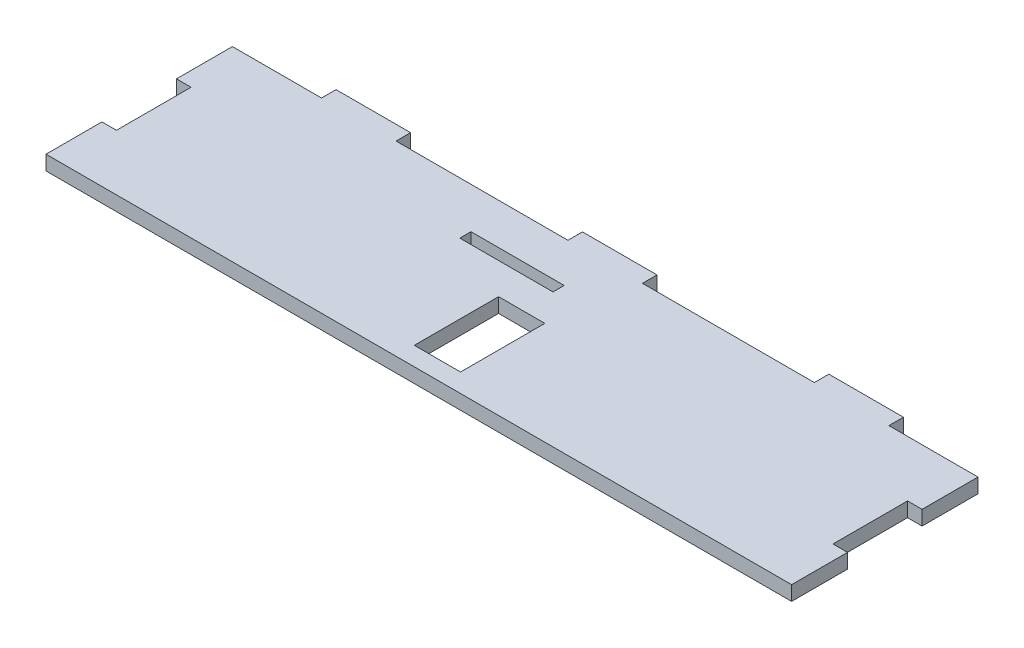
SolidWorks part; units mm, degrees
material "Very Low Density PE (SS)"
ref_plane "Front Plane" through (0, 0, 0) normal (0, 0, 1) x (1, 0, 0)
ref_plane "Top Plane" through (0, 0, 0) normal (0, 1, 0) x (1, 0, 0)
ref_plane "Right Plane" through (0, 0, 0) normal (1, 0, 0) x (0, 0, -1)
sketch "Sketch1" plane through (0, 0, 0) normal (0, 1, 0) x (1, 0, 0)
  line L0 (0, -25) -> (0, 26.95) construction
  line L1 (-100, 25) -> (-76.1, 25)
  line L2 (-100, 25) -> (-100, 10)
  line L3 (-100, -25) -> (100, -25)
  line L4 (100, 25) -> (100, 10)
  line L5 (-100, 25) -> (100, -25) construction
  line L6 (-100, -25) -> (100, 25) construction
  line L7 (76.1, 28.9) -> (56.1, 28.9)
  line L9 (-76.1, 25) -> (-76.1, 28.9)
  line L10 (-76.1, 28.9) -> (-56.1, 28.9)
  line L11 (-56.1, 25) -> (-56.1, 28.9)
  line L12 (56.1, 25) -> (56.1, 28.9)
  line L14 (76.1, 25) -> (76.1, 28.9)
  line L15 (-56.1, 25) -> (-10, 25)
  line L16 (76.1, 25) -> (100, 25)
  line L17 (10, 25) -> (56.1, 25)
  line L18 (-10, 28.9) -> (10, 28.9)
  line L19 (-10, 28.9) -> (-10, 25)
  line L21 (10, 28.9) -> (10, 25)
  line L22 (-10, 28.9) -> (10, 25) construction
  line L23 (-10, 25) -> (10, 28.9) construction
  line L24 (-100, 0) -> (100, 0) construction
  line L29 (-100, -5) -> (-100, 5)
  line L31 (100, 10) -> (96.1, 10)
  line L35 (-100, 5) -> (-100, -5) construction
  line L36 (-100, -5) -> (-100, 0)
  line L37 (100, 5) -> (100, -5) construction
  line L39 (100, 10) -> (100, 0) construction
  line L43 (100, -10) -> (96.1, -10)
  line L44 (100, -10) -> (100, 0) construction
  line L45 (-100, -10) -> (-100, 0) construction
  line L46 (-100, -10) -> (-96.1, -10)
  line L47 (-96.1, -10) -> (-96.1, 0)
  line L48 (-100, 0) -> (-96.1, 0)
  line L49 (-100, 0) -> (-96.1, 0)
  line L50 (-96.1, 10) -> (-96.1, 0)
  line L51 (-100, 10) -> (-96.1, 10)
  line L52 (-100, 10) -> (-100, 0) construction
  line L53 (100, 10) -> (100, 0) construction
  line L55 (100, 0) -> (100, -10) construction
  line L56 (100, -10) -> (100, -25)
  line L57 (-100, 10) -> (-100, 0) construction
  line L58 (-100, 0) -> (-100, 5)
  line L59 (-100, 0) -> (-100, -10) construction
  line L60 (-100, -10) -> (-100, -25)
  line L61 (0, 11) -> (-25, 11)
  line L62 (-6.2, 2.6) -> (6.2, 2.6)
  line L63 (-6.2, 2.6) -> (-6.2, -20)
  line L64 (-6.2, -20) -> (6.2, -20)
  line L65 (6.2, 2.6) -> (6.2, -20)
  line L66 (-6.2, 2.6) -> (6.2, -20) construction
  line L67 (-6.2, -20) -> (6.2, 2.6) construction
  line L72 (-25, 14) -> (-25, 11)
  line L73 (0, 14) -> (-25, 14)
  line L74 (0, 14) -> (0, 11)
  line L75 (96.1, 10) -> (96.1, -10)
  point P0 (0, 0)
  point P18 (0, 26.95)
  point P43 (0, -8.7)
  dimension "D8" = 20
  dimension "D10" = 22.6
  dimension "D12" = 5
  dimension "D1" = 200
  dimension "D2" = 50
  dimension "D3" = 20
  dimension "D4" = 3.9
  dimension "D5" = 23.9
  dimension "D6" = 20
  dimension "D7" = 3.9
  dimension "D9" = 11
  dimension "D11" = 12.4
  dimension "D13" = 25
  dimension "D14" = 3
extrude "Boss-Extrude1" add sketch "Sketch1" along normal blind 3.9 contours L46 L60 L3 L56 L43 L31 L4 L16 L14 L7 L12 L17 L21 L18 L19 L15 L11 L10 L9 L1 L2 L51 L50 L49 L58 L29 L36 L48 L47 L62 L65 L64 L63 L73 L74 L61 L72 | L65 L62 L63 L64 region at (-88.05, 0, -22.9286) region at (0, 0, 8.7)
extrude "Cut-Extrude3" cut sketch "Sketch1<3>" along normal through all contours L65 L62 L63 L64 region at (0, 0, 8.7)
sketch "Sketch1<3>" plane through (0, 0, 0) normal (0, 1, 0) x (1, 0, 0) same geometry as "Sketch1"
